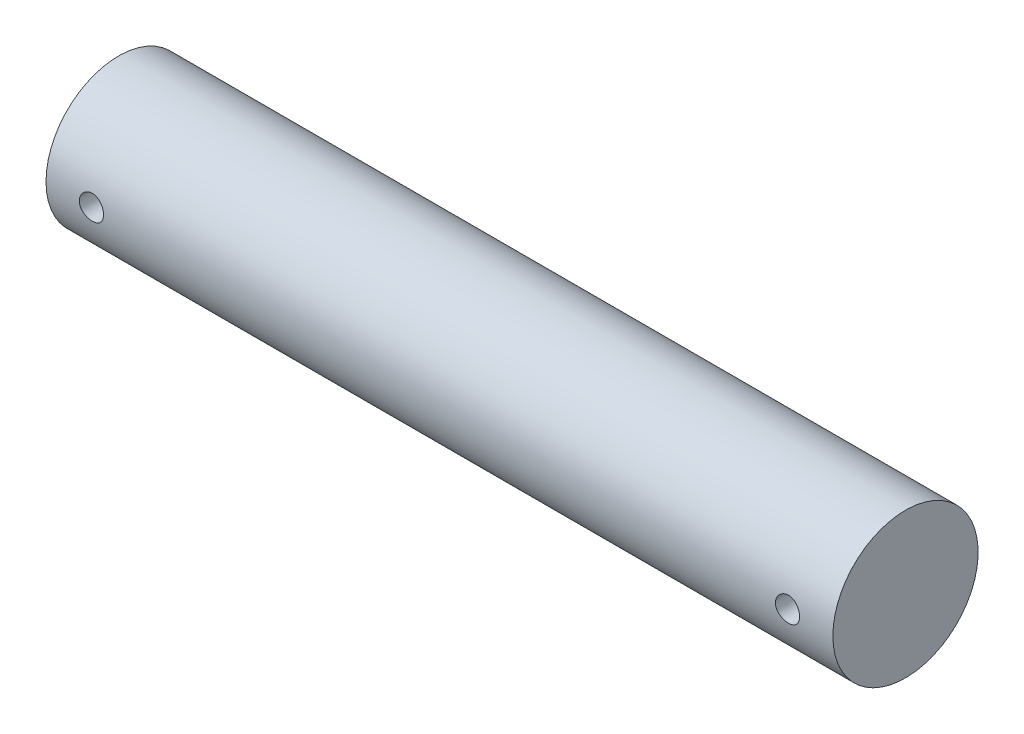
SolidWorks part; units mm, degrees
ref_plane "Front Plane" through (0, 0, 0) normal (0, 0, 1) x (1, 0, 0)
ref_plane "Top Plane" through (0, 0, 0) normal (0, 1, 0) x (1, 0, 0)
ref_plane "Right Plane" through (0, 0, 0) normal (1, 0, 0) x (0, 0, -1)
sketch "Sketch1" plane through (0, 0, 0) normal (0, 1, 0) x (1, 0, 0)
  line L0 (0, 0) -> (130, 0)
  line L21 (0, 0) -> (0, 12)
  line L22 (0, 12) -> (130, 12)
  line L27 (130, 12) -> (130, 0)
  dimension "D1" = 12
  dimension "D2" = 130
revolve "Revolve1" add sketch "Sketch1" angle 360 about L0
sketch "Sketch2" plane through (0, 0, 0) normal (0, 0, 1) x (1, 0, 0)
  line L0 (130, -12) -> (130, 12) construction
  circle A0 centre (7.5, 0) radius 2
  circle A1 centre (122.5, 0) radius 2
  dimension "D1" = 4
  dimension "D2" = 115
  dimension "4" = 4
  dimension "D3" = 7.5
  dimension "D4" = 7.5
extrude "Cut-Extrude4" cut sketch "Sketch2" against normal blind 12 and the other way blind 12 contours A0 | A1
